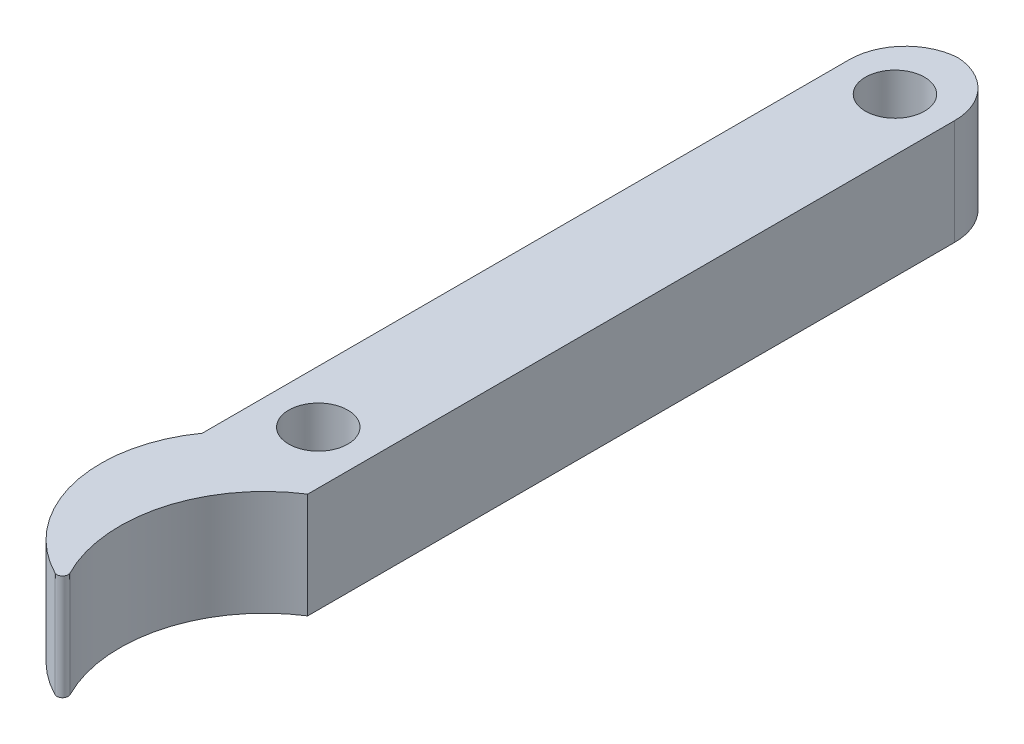
SolidWorks part; units mm, degrees
material "PVC Rigid"
ref_plane "Front Plane" through (0, 0, 0) normal (0, 0, 1) x (1, 0, 0)
ref_plane "Top Plane" through (0, 0, 0) normal (0, 1, 0) x (1, 0, 0)
ref_plane "Right Plane" through (0, 0, 0) normal (1, 0, 0) x (0, 0, -1)
sketch "Sketch1" plane through (0, 0, 0) normal (0, 1, 0) x (1, 0, 0)
  line L0 (0, 26.035) -> (0, 0) construction
  line L1 (-4.7625, 31.75) -> (4.7625, 31.75)
  line L2 (-4.7625, 31.75) -> (-4.7625, -31.75)
  line L3 (-4.7625, -31.75) -> (4.7625, -31.75) construction
  line L4 (4.7625, 31.75) -> (4.7625, -31.75)
  line L5 (-4.7625, 31.75) -> (4.7625, -31.75) construction
  line L6 (-4.7625, -31.75) -> (4.7625, 31.75) construction
  line L7 (0, 0) -> (0, -26.035) construction
  circle A0 centre (0, -26.035) radius 2.667
  circle A1 centre (0, 26.035) radius 2.667
  arc A2 (-4.7625, -31.75) -> (0.9525, -49.9435) centre (4.9691, -38.6874) ccw
  arc A3 (0.9525, -49.9435) -> (4.7625, -31.75) centre (11.8186, -42.7234) cw
  point P0 (0, 0)
  dimension "D3" = 5.334
  dimension "D5" = 18.1935
  dimension "D6" = 13.0462
  dimension "D7" = 11.9513
  dimension "D1" = 63.5
  dimension "D2" = 52.07
  dimension "D4" = 9.525
  dimension "D8" = 3.81
extrude "Boss-Extrude1" add sketch "Sketch1" along normal blind 9.525
fillet "Fillet1" radius 5.08 2 edges at (-4.7625, 4.7625, -31.75) (4.7625, 4.7625, -31.75)
sketch "Sketch2" plane through (0, 0, 0) normal (0, -1, 0) x (1, 0, 0)
  circle A0 centre (0, 26.035) radius 6.35
  dimension "D1" = 12.7
extrude "Cut-Extrude1" [suppressed] cut sketch "Sketch2" against normal blind 4.4018
fillet "Fillet2" radius 0.508 1 edges at (0.9525, 4.7625, 49.9435)
